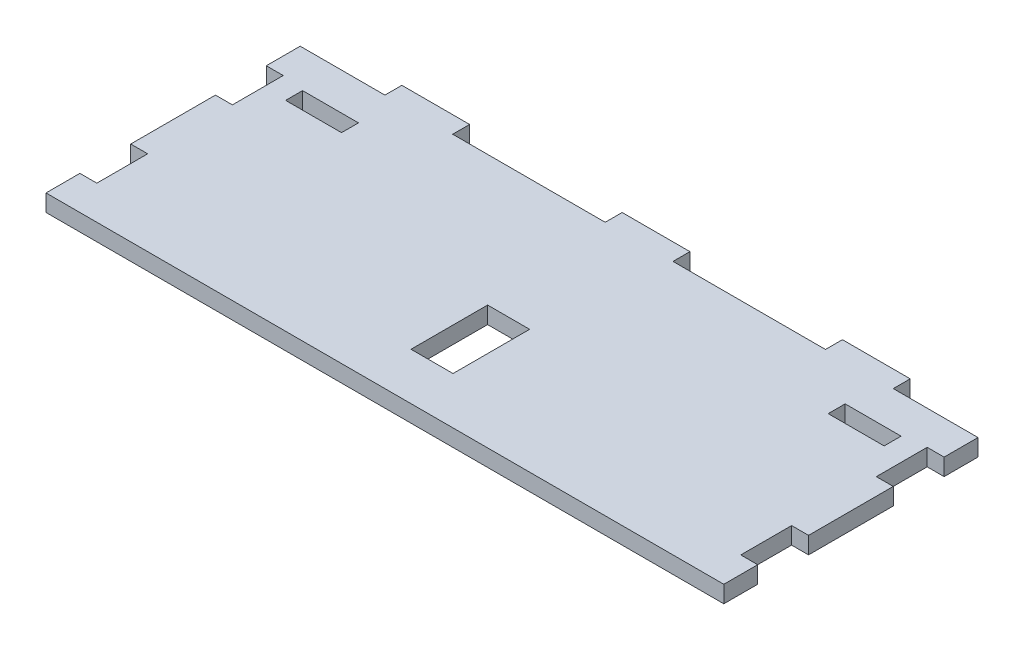
SolidWorks part; units mm, degrees
ref_plane "Front Plane" through (0, 0, 0) normal (0, 0, 1) x (1, 0, 0)
ref_plane "Top Plane" through (0, 0, 0) normal (0, 1, 0) x (1, 0, 0)
ref_plane "Right Plane" through (0, 0, 0) normal (1, 0, 0) x (0, 0, -1)
sketch "Sketch1" plane through (0, 0, 0) normal (0, 1, 0) x (1, 0, 0)
  line L0 (0, -37.5) -> (0, 40) construction
  line L1 (-100, 37.5) -> (-75, 37.5)
  line L2 (-100, 37.5) -> (-100, 27.5)
  line L3 (-100, -37.5) -> (100, -37.5)
  line L4 (100, 37.5) -> (100, 27.5)
  line L5 (-100, 37.5) -> (100, -37.5) construction
  line L6 (-100, -37.5) -> (100, 37.5) construction
  line L7 (75, 42.5) -> (55, 42.5)
  line L9 (-75, 37.5) -> (-75, 42.5)
  line L10 (-75, 42.5) -> (-55, 42.5)
  line L11 (-55, 37.5) -> (-55, 42.5)
  line L12 (55, 37.5) -> (55, 42.5)
  line L14 (75, 37.5) -> (75, 42.5)
  line L15 (-55, 37.5) -> (-10, 37.5)
  line L16 (75, 37.5) -> (100, 37.5)
  line L17 (10, 37.5) -> (55, 37.5)
  line L18 (-10, 42.5) -> (10, 42.5)
  line L19 (-10, 42.5) -> (-10, 37.5)
  line L21 (10, 42.5) -> (10, 37.5)
  line L22 (-10, 42.5) -> (10, 37.5) construction
  line L23 (-10, 37.5) -> (10, 42.5) construction
  line L24 (-100, 0) -> (100, 0) construction
  line L29 (-100, -5) -> (-100, 5)
  line L30 (100, -12.5) -> (95, -12.5)
  line L31 (100, 27.5) -> (95, 27.5)
  line L32 (100, -5) -> (100, 5)
  line L35 (-100, 5) -> (-100, -5) construction
  line L36 (-100, -5) -> (-100, -12.5)
  line L37 (100, 5) -> (100, -5) construction
  line L38 (100, -5) -> (100, -12.5)
  line L39 (100, 27.5) -> (100, 12.5) construction
  line L40 (100, 12.5) -> (95, 12.5)
  line L41 (95, 27.5) -> (95, 12.5)
  line L42 (95, -27.5) -> (95, -12.5)
  line L43 (100, -27.5) -> (95, -27.5)
  line L44 (100, -27.5) -> (100, -12.5) construction
  line L45 (-100, -27.5) -> (-100, -12.5) construction
  line L46 (-100, -27.5) -> (-95, -27.5)
  line L47 (-95, -27.5) -> (-95, -12.5)
  line L48 (-100, -12.5) -> (-95, -12.5)
  line L49 (-100, 12.5) -> (-95, 12.5)
  line L50 (-95, 27.5) -> (-95, 12.5)
  line L51 (-100, 27.5) -> (-95, 27.5)
  line L52 (-100, 27.5) -> (-100, 12.5) construction
  line L53 (100, 27.5) -> (100, 12.5) construction
  line L54 (100, 12.5) -> (100, 5)
  line L55 (100, -12.5) -> (100, -27.5) construction
  line L56 (100, -27.5) -> (100, -37.5)
  line L57 (-100, 27.5) -> (-100, 12.5) construction
  line L58 (-100, 12.5) -> (-100, 5)
  line L59 (-100, -12.5) -> (-100, -27.5) construction
  line L60 (-100, -27.5) -> (-100, -37.5)
  line L61 (88.3, 21.5) -> (71.8, 21.5)
  line L62 (-6.2, -1) -> (6.2, -1)
  line L63 (-6.2, -1) -> (-6.2, -23.6)
  line L64 (-6.2, -23.6) -> (6.2, -23.6)
  line L65 (6.2, -1) -> (6.2, -23.6)
  line L66 (-6.2, -1) -> (6.2, -23.6) construction
  line L67 (-6.2, -23.6) -> (6.2, -1) construction
  line L68 (-88.3, 26.5) -> (-71.8, 26.5)
  line L69 (-88.3, 26.5) -> (-88.3, 21.5)
  line L70 (-88.3, 21.5) -> (-71.8, 21.5)
  line L71 (-71.8, 26.5) -> (-71.8, 21.5)
  line L72 (71.8, 26.5) -> (71.8, 21.5)
  line L73 (88.3, 26.5) -> (71.8, 26.5)
  line L74 (88.3, 26.5) -> (88.3, 21.5)
  point P0 (0, 0)
  point P18 (0, 40)
  point P43 (0, -12.3)
  dimension "D8" = 5
  dimension "D10" = 22.6
  dimension "D12" = 1
  dimension "D1" = 200
  dimension "D2" = 75
  dimension "D3" = 20
  dimension "D4" = 5
  dimension "D5" = 25
  dimension "D6" = 20
  dimension "D7" = 15
  dimension "D9" = 10
  dimension "D11" = 12.4
  dimension "D13" = 16.5
  dimension "D14" = 5
  dimension "D15" = 6.7
  dimension "D16" = 11
extrude "Boss-Extrude1" add sketch "Sketch1" along normal blind 5 contours L46 L60 L3 L56 L43 L42 L30 L38 L32 L54 L40 L41 L31 L4 L16 L14 L7 L12 L17 L21 L18 L19 L15 L11 L10 L9 L1 L2 L51 L50 L49 L58 L29 L36 L48 L47 L62 L65 L64 L63 L68 L71 L70 L69 L73 L74 L61 L72 | L65 L62 L63 L64 region at (0, 0, -0.7892) region at (0, 0, 12.3)
extrude "Cut-Extrude3" cut sketch "Sketch1<3>" along normal through all contours L65 L62 L63 L64 region at (0, 0, 12.3)
sketch "Sketch1<3>" plane through (0, 0, 0) normal (0, 1, 0) x (1, 0, 0) same geometry as "Sketch1"
